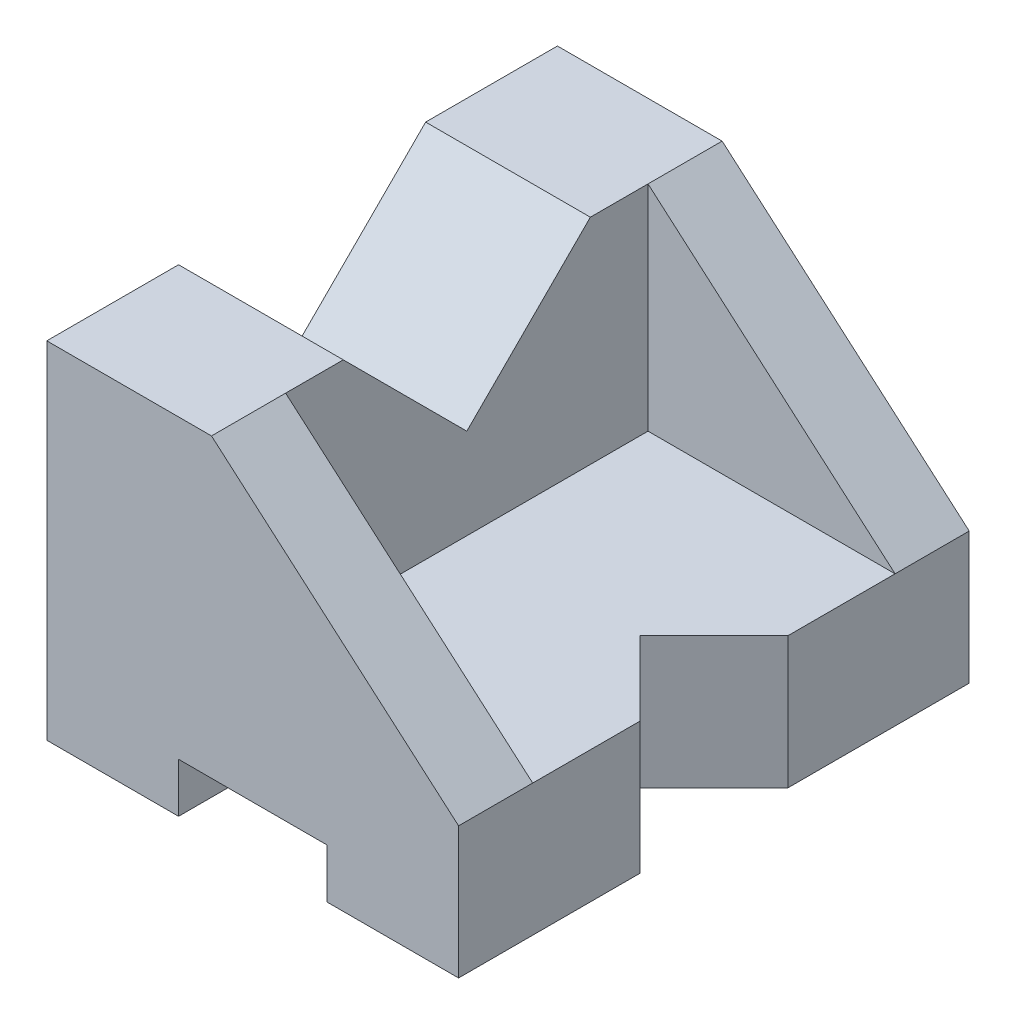
SolidWorks part; units mm, degrees
ref_plane "Front Plane" through (0, 0, 0) normal (0, 0, 1) x (1, 0, 0)
ref_plane "Top Plane" through (0, 0, 0) normal (0, 1, 0) x (1, 0, 0)
ref_plane "Right Plane" through (0, 0, 0) normal (1, 0, 0) x (0, 0, -1)
sketch "Sketch1" plane through (0, 0, 0) normal (0, 0, 1) x (1, 0, 0)
  line L0 (0, 42) -> (0, 0)
  line L1 (0, 0) -> (16, 0)
  line L2 (50, 0) -> (50, 16)
  line L3 (50, 16) -> (20, 42)
  line L4 (20, 42) -> (0, 42)
  line L5 (16, 0) -> (16, 6)
  line L6 (16, 6) -> (34, 6)
  line L7 (34, 6) -> (34, 0)
  line L8 (34, 0) -> (50, 0)
  line L9 (20, 42) -> (20, 16)
  line L10 (20, 16) -> (50, 16)
  point P9 (34, 3)
  dimension "D1" = 42
  dimension "D2" = 50
  dimension "D3" = 16
  dimension "D4" = 20
  dimension "D5" = 16
  dimension "D6" = 16
  dimension "D7" = 6
extrude "Boss-Extrude1" add sketch "Sketch1" along normal mid plane 62 contours L10 L9 L4 L0 L1 L5 L6 L7 L8 L2 region at (18.5644, 17.4554, 0)
extrude "Boss-Extrude2" add sketch "Sketch1<3>" along normal blind 9 from offset 22 contours L9 L10 L3 region at (30, 24.6667, 0)
sketch "Sketch1<3>" plane through (0, 0, 0) normal (0, 0, 1) x (1, 0, 0) same geometry as "Sketch1"
extrude "Boss-Extrude3" add sketch "Sketch1<5>" against normal blind 9 from offset 22 contours L9 L10 L3 region at (30, 24.6667, 0) offset against normal yes
sketch "Sketch1<5>" plane through (0, 0, 0) normal (0, 0, 1) x (1, 0, 0) same geometry as "Sketch1"
sketch "Sketch3" plane through (20, 0, 0) normal (1, 0, 0) x (0, 0, -1)
  line L0 (-15, 42) -> (0, 27)
  line L1 (-22, 42) -> (22, 42) construction
  line L2 (0, 27) -> (15, 42)
  line L6 (22, 42) -> (22, 16) construction
  line L7 (-15, 42) -> (15, 42)
  dimension "D1" = 30
  dimension "D2" = 15
  dimension "D3" = 16
  dimension "D4" = 22
extrude "Cut-Extrude1" cut sketch "Sketch3" against normal blind 39 contours L7 L2 L0
sketch "Sketch4" plane through (0, 16, 0) normal (0, 1, 0) x (1, 0, 0)
  line L0 (50, 9) -> (41, 0)
  line L1 (50, -22) -> (50, 22) construction
  line L2 (-23.1, 0) -> (23.1, 0) construction
  line L3 (41, 0) -> (50, -9)
  line L5 (50, 9) -> (50, -9)
  dimension "D1" = 18
  dimension "D2" = 13
  dimension "D3" = 9
extrude "Cut-Extrude2" cut sketch "Sketch4" against normal blind 39
